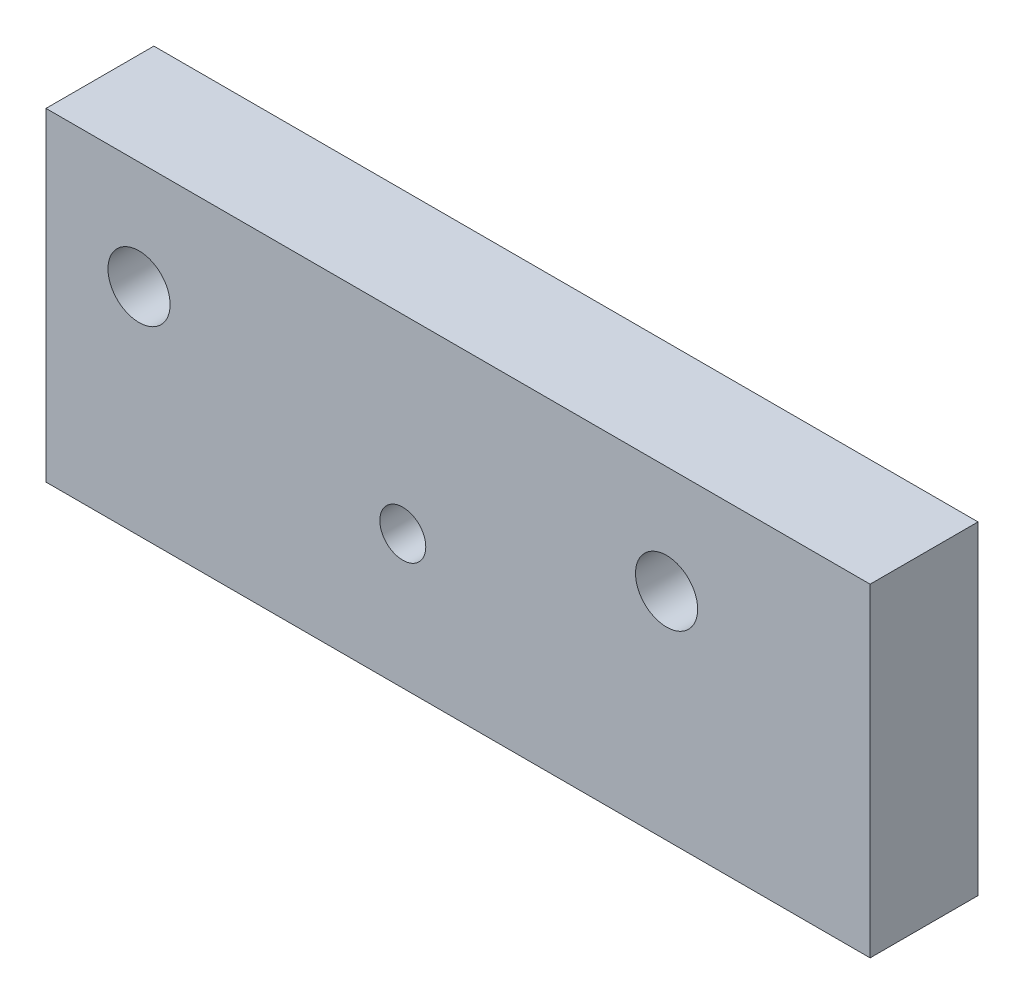
SolidWorks part; units mm, degrees
material "6061-T6 (SS)"
ref_plane "Front" through (0, 0, 0) normal (0, 0, 1) x (1, 0, 0)
ref_plane "Top" through (0, 0, 0) normal (0, 1, 0) x (1, 0, 0)
ref_plane "Right" through (0, 0, 0) normal (1, 0, 0) x (0, 0, -1)
ref_axis "side-side" through (80.9, 0, 0) along (-1, 0, 0)
ref_axis "up-down" through (0, 50, 0) along (0, -1, 0)
ref_axis "front-back" through (0, 0, -80.9) along (0, 0, 1)
sketch "Sketch1" plane through (0, 0, 0) normal (0, 0, 1) x (1, 0, 0)
  line L0 (0, -50) -> (0, 50) construction
  line L1 (-21, 6.35) -> (27.505, 6.35)
  line L2 (-21, 6.35) -> (-21, -12.7)
  line L3 (-21, -12.7) -> (27.505, -12.7)
  line L4 (27.505, 6.35) -> (27.505, -12.7)
  dimension "D1" = 19.05
  dimension "D2" = 48.505
  dimension "D3" = 6.35
  dimension "D4" = 21
  dimension "D5" = 27.505
extrude "Boss-Extrude1" add sketch "Sketch1" along normal blind 6.35
hole_wizard "#6 Clearance Hole1" positions "Sketch2" profile "Sketch3" hole size "#6" standard "ANSI Inch"
sketch "Sketch2" plane through (0, 0, 6.35) normal (0, 0, 1) x (1, 0, 0)
  line L0 (-15.525, 0) -> (15.525, 0) construction
  point P0 (-15.525, 0)
  point P1 (15.525, 0)
  dimension "D1" = 31.05
sketch "Sketch3" plane through (-15.525, 0, 6.35) normal (1, 0, 0) x (0, -1, 0)
  line L0 (0, 0) -> (0, 10.4969)
  line L1 (0, 10.4969) -> (1.8288, 9.398)
  line L2 (1.8288, 9.398) -> (1.8288, 0)
  line L5 (1.8288, 0) -> (0, 0)
  line L10 (0, 10.4969) -> (-1.8288, 9.398) construction
  line L11 (0, -6.35) -> (0, 107.95) construction
  dimension "Hole Dia." = 3.6576
  dimension "Hole Depth" = 9.398
  dimension "Drill Angle" = 118
sketch "Sketch4" plane through (0, 0, 0) normal (0, 0, -1) x (-1, 0, 0)
  circle A0 centre (-15.525, 0) radius 4.7625
  circle A1 centre (15.525, 0) radius 4.7625
  dimension "D1" = 9.525
extrude "Cut-Extrude1" cut sketch "Sketch4" against normal blind 2
sketch3d "3DSketch1"
  circle A1 centre (0, -4.8294, -0.15) radius 1.905
  point P4 (0, -4.8294, 1.755)
hole_wizard "#6-32 Tapped Hole1" positions "Sketch5" profile "Sketch6" tap size "#6-32" standard "ANSI Inch"
sketch "Sketch5" plane through (0, 0, 0) normal (0, 0, -1) x (-1, 0, 0)
  point P0 (0, -4.8294)
sketch "Sketch6" plane through (0, -4.8294, 0) normal (1, 0, 0) x (0, 1, 0)
  line L0 (0, 0) -> (0, 11.7855)
  line L1 (0, 11.7855) -> (1.3525, 10.9728)
  line L2 (1.3525, 10.9728) -> (1.3525, 0)
  line L5 (1.3525, 0) -> (0, 0)
  line L10 (0, 11.7855) -> (-1.3526, 10.9728) construction
  line L11 (0, -6.35) -> (0, 107.95) construction
  dimension "Tap Drill Dia." = 2.7051
  dimension "Tap Drill Depth" = 10.9728
  dimension "Drill Angle" = 118
